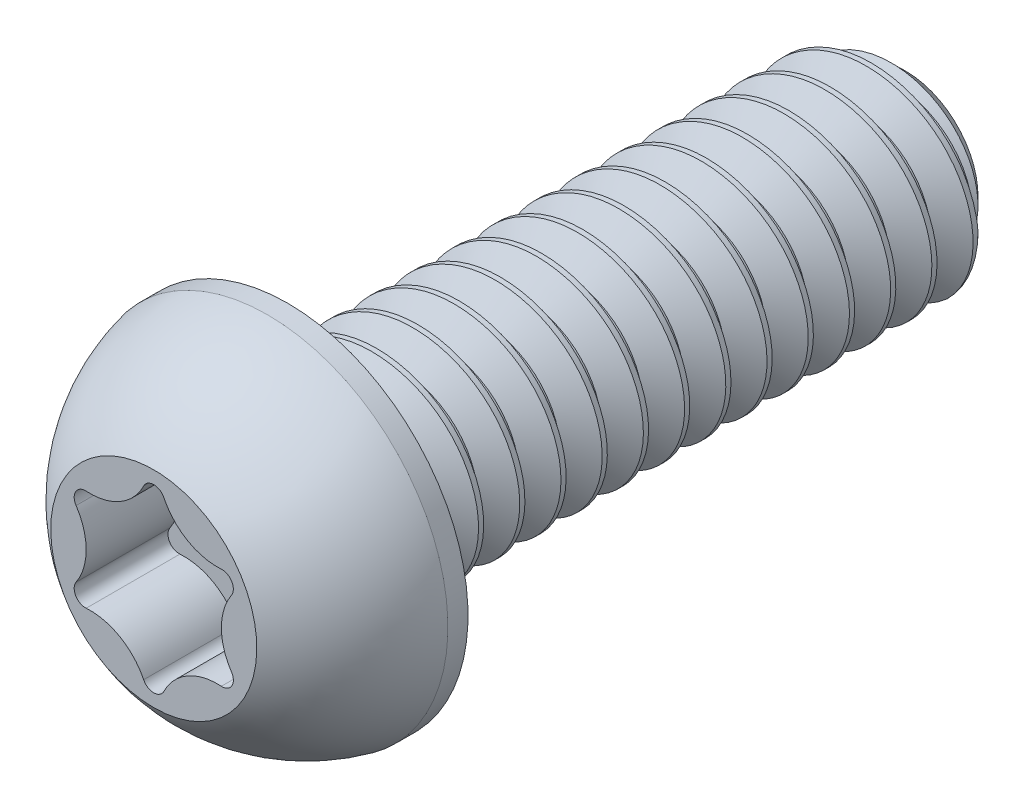
SolidWorks part; units mm, degrees
material "Alloy Steel"
ref_plane "Front" through (0, 0, 0) normal (0, 0, 1) x (1, 0, 0)
ref_plane "Top" through (0, 0, 0) normal (0, 1, 0) x (1, 0, 0)
ref_plane "Right" through (0, 0, 0) normal (1, 0, 0) x (0, 0, -1)
sketch "Sketch1" plane through (0, 0, 0) normal (1, 0, 0) x (0, 0, -1)
  line L2 (-3, 1) -> (3, 1)
  line L3 (3, 1) -> (3, 0)
  line L4 (3, 0) -> (-3, 0)
  line L6 (-3.195, 1.75) -> (-3, 1.75) construction
  line L7 (3, 1) -> (3, -1) construction
  line L8 (-4.3, 0) -> (-3, 0) construction
  line L9 (-3, 1.75) -> (-3, -1.75) construction
  line L11 (-3, 1) -> (-3, 0)
  line L14 (-4.3, 0) -> (-4.3, 1) construction
  line L15 (3, -1) -> (2.6, -1) construction
  arc A3 (-4.3, 1) -> (-3.195, 1.75) centre (-2.8142, 0) cw construction
  point P10 (2.4, -1)
  point P15 (0, 0)
  dimension "Thread OD" = 2
  dimension "D1" = 0.195
  dimension "Head Height" = 1.3
  dimension "Head Diameter" = 3.5
  dimension "Length" = 6
  dimension "Thread Pitch" = 0.4
  dimension "D2" = 0.6
sketch "Sketch2" plane through (0, 0, 0) normal (0, 0, 1) x (1, 0, 0)
  line L0 (0, 0) -> (-0.7578, 0.4375)
  line L1 (0, 0) -> (-0.7578, -0.4375)
  line L2 (0, 0.875) -> (0, 0.7656) construction
  line L3 (0, 0.7656) -> (0, 0.6563) construction
  circle A0 centre (0, 0) radius 0.875 construction
  circle A1 centre (0, 0) radius 0.6563 construction
  circle A2 centre (0, 0) radius 0.7656 construction
  arc A4 (-0.754, 0.322) -> (-0.754, -0.322) centre (-1.2357, 0) cw
  arc A5 (-0.754, 0.322) -> (-0.7578, 0.4375) centre (-0.6631, 0.3828) cw
  arc A6 (-0.754, -0.322) -> (-0.7578, -0.4375) centre (-0.6631, -0.3828) ccw
  point P3 (0, -0.875)
  dimension "Torx OD" = 1.75
  dimension "D1" = 1.3125
  dimension "D2" = 60
sketch "Sketch12" plane through (0, 0, 0) normal (1, 0, 0) x (0, 0, -1)
  line L0 (-3, 1) -> (-3, 0) construction
  line L1 (3, 0) -> (-3, 0) construction
  line L2 (3, 1) -> (3, 0) construction
  line L3 (-3, 1) -> (3, 1) construction
  line L4 (-3, 1) -> (-3, 0)
  line L5 (3, 0) -> (-3, 0)
  line L6 (3, 1) -> (3, 0)
  line L7 (-3, 1) -> (3, 1)
revolve "Revolve1" add sketch "Sketch12" angle 360 about L5
sketch "Sketch7" plane through (0, 0, 0) normal (1, 0, 0) x (0, 0, -1)
  line L0 (-4.3, 0) -> (-4.3, 1) construction
  line L6 (-3.195, 1.75) -> (-3, 1.75) construction
  line L8 (-4.3, 0) -> (-3, 0) construction
  line L11 (-3, 1.75) -> (-3, -1.75) construction
  line L12 (-3.195, 1.75) -> (-3, 1.75)
  line L13 (-4.3, 0) -> (-3, 0)
  line L15 (-3, 1.75) -> (-3, 0)
  line L16 (-4.3, 1) -> (-4.3, 0)
  arc A2 (-3.195, 1.75) -> (-4.3, 1) centre (-2.8142, 0) ccw construction
  arc A3 (-3.195, 1.75) -> (-4.3, 1) centre (-2.8142, 0) ccw
revolve "Revolve2" add sketch "Sketch7" angle 360 mid plane about L13
sketch "Sketch11" plane through (0, 0, 4.3) normal (0, 0, 1) x (1, 0, 0)
  line L0 (0, 0) -> (-0.7578, 0.4375) construction
  line L1 (0, 0) -> (-0.7578, -0.4375) construction
  line L2 (0, 0) -> (-0.7578, 0.4375)
  line L3 (0, 0) -> (-0.7578, -0.4375)
  arc A0 (-0.7578, 0.4375) -> (-0.754, 0.322) centre (-0.6631, 0.3828) ccw construction
  arc A1 (-0.754, -0.322) -> (-0.754, 0.322) centre (-1.2357, 0) ccw construction
  arc A3 (-0.754, -0.322) -> (-0.7578, -0.4375) centre (-0.6631, -0.3828) ccw construction
  arc A4 (-0.7578, 0.4375) -> (-0.754, 0.322) centre (-0.6631, 0.3828) ccw
  arc A5 (-0.754, -0.322) -> (-0.754, 0.322) centre (-1.2357, 0) ccw
  arc A7 (-0.754, -0.322) -> (-0.7578, -0.4375) centre (-0.6631, -0.3828) ccw
extrude "Cut-Extrude4" cut sketch "Sketch11" against normal blind 0.91
pattern_circular "CirPattern1" count 6 over 360 of "Cut-Extrude4"
chamfer "Chamfer1" distance 0.3 angle 45 1 edges at (0, 1, -3)
split "Split1" bodies to split 122 113 resulting bodies 125 126 split by face at (0, -1, 3)
sketch "Sketch13" plane through (0, 0, -3) normal (0, 0, -1) x (-1, 0, 0)
  circle A0 centre (0, 0) radius 1 construction
  circle A1 centre (0, 0) radius 1
curve "Helix/Spiral1" pitch 0.4 height 6.4 radius 1 centre (0, 0, -3) axis (0, 0, 1) start towards (0, 1, 0)
sketch "Sketch14" plane through (0, 0, 0) normal (1, 0, 0) x (0, 0, -1)
  line L0 (3.375, 1.0433) -> (2.975, 1.0433) construction
  line L1 (2.975, 1.0433) -> (3.175, 0.6969) construction
  line L2 (3.175, 0.6969) -> (3.375, 1.0433) construction
  line L3 (3.35, 1) -> (3, 1) construction
  line L4 (3.175, 1.0433) -> (3.175, 1) construction
  line L5 (3.3625, 1.0217) -> (2.9875, 1.0217) construction
  line L6 (3.2, 0.7402) -> (3.15, 0.7402) construction
  line L7 (3.175, 0.7402) -> (3.175, 0.6969) construction
  line L8 (3.15, 0.7402) -> (2.9875, 1.0217)
  line L9 (2.9875, 1.0217) -> (3.3625, 1.0217)
  line L10 (3.3625, 1.0217) -> (3.2, 0.7402)
  line L11 (3.2, 0.7402) -> (3.15, 0.7402)
  point P11 (3.175, 1.0217)
  dimension "D1" = 0.4
  dimension "D2" = 0.05
sweep "Cut-Sweep1" cut profiles "Sketch14" path "Helix/Spiral1" align with end faces yes
combine bodies "Combine1" operation type add bodies to combine 125 127
equation "\"D3@Helix/Spiral1\" = \"Length@Sketch1\" + \"Thread Pitch@Sketch1\""
equation "\"D1@Chamfer1\"=\"D4@Helix/Spiral1\" * .75"
equation "\"D1@Sketch1\" = \"Head Height@Sketch1\" * .15"
equation "\"D1@Cut-Extrude4\" = \"Head Height@Sketch1\" * .7"
equation "\"D2@Sketch1\"=\"Thread Pitch@Sketch1\"*1.5"
equation "\"D1@Sketch14\"=\"Thread Pitch@Sketch1\""
equation "\"D2@Sketch14\"=\"D1@Sketch14\"/ 1/8"
equation "\"D4@Helix/Spiral1\"=\"Thread Pitch@Sketch1\""
equation "\"D1@Sketch2\"=\"Torx OD@Sketch2\"*.75"
